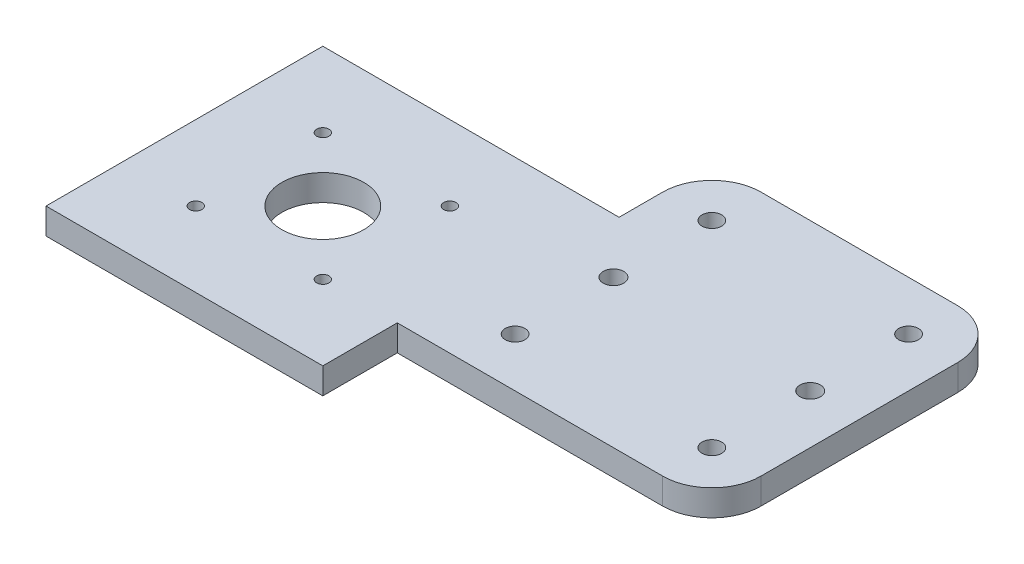
SolidWorks part; units mm, degrees
ref_plane "Front Plane" through (0, 0, 0) normal (0, 0, 1) x (1, 0, 0)
ref_plane "Top Plane" through (0, 0, 0) normal (0, 1, 0) x (1, 0, 0)
ref_plane "Right Plane" through (0, 0, 0) normal (1, 0, 0) x (0, 0, -1)
sketch "Sketch1" plane through (0, 0, 0) normal (0, 1, 0) x (1, 0, 0)
  line L1 (-24, -36) -> (24, -36)
  line L2 (-36, -24) -> (-36, 24)
  line L3 (-24, 36) -> (24, 36)
  line L4 (36, -24) -> (36, 24)
  line L5 (-36, -36) -> (36, 36) construction
  line L6 (-36, 36) -> (36, -36) construction
  arc A0 (24, 36) -> (36, 24) centre (24, 24) cw
  arc A1 (24, -36) -> (36, -24) centre (24, -24) ccw
  arc A2 (-24, -36) -> (-36, -24) centre (-24, -24) cw
  arc A3 (-36, 24) -> (-24, 36) centre (-24, 24) cw
  point P0 (0, 0)
  dimension "D1" = 12
  dimension "D2" = 72
  dimension "D3" = 72
extrude "Boss-Extrude1" add sketch "Sketch1" along normal blind 6.35
sketch "Sketch2" plane through (0, 6.35, 0) normal (0, 1, 0) x (1, 0, 0)
  line L0 (-36, 0) -> (36, 0) construction
  line L1 (-36, 24) -> (-36, -24) construction
  line L2 (36, -24) -> (36, 24) construction
  line L3 (-36, 12) -> (36, 12) construction
  circle A0 centre (-24, 24) radius 12 construction
  circle A1 centre (-24, 24) radius 2.4
  arc A2 (-24, 36) -> (-36, 24) centre (-24, 24) ccw construction
  circle A3 centre (24, 24) radius 2.4
  circle A4 centre (24, -24) radius 2.4
  circle A5 centre (-24, -24) radius 2.4
  dimension "D3" = 4.8
  dimension "D1" = 24
  dimension "D2" = 2
  dimension "D4" = 2
extrude "Cut-Extrude1" cut sketch "Sketch2" against normal through all
sketch "Sketch3" plane through (0, 6.35, 0) normal (0, 1, 0) x (1, 0, 0)
  line L0 (-24, 0) -> (24, 0) construction
  line L1 (-24, 24) -> (-24, -24) construction
  line L2 (24, 24) -> (24, -24) construction
  circle A1 centre (-24, 0) radius 2.5
  circle A3 centre (24, 0) radius 2.5
  dimension "D1" = 5
extrude "Cut-Extrude2" cut sketch "Sketch3" against normal through all
sketch "Sketch4" plane through (0, 6.35, 0) normal (0, 1, 0) x (1, 0, 0)
  line L11 (-108.286, -54.1706) -> (-40.7474, -54.1706)
  line L12 (-108.286, -54.1706) -> (-108.286, 13.368)
  line L13 (-108.286, 13.368) -> (-36, 13.368)
  line L14 (-40.7474, -54.1706) -> (-40.7474, -36)
  line L15 (-108.286, -54.1706) -> (-40.7474, 13.368) construction
  line L16 (-108.286, 13.368) -> (-40.7474, -54.1706) construction
  line L17 (-90.0167, -35.9013) -> (-59.0167, -35.9013) construction
  line L18 (-90.0167, -35.9013) -> (-90.0167, -4.9013) construction
  line L19 (-90.0167, -4.9013) -> (-59.0167, -4.9013) construction
  line L20 (-59.0167, -35.9013) -> (-59.0167, -4.9013) construction
  line L21 (-90.0167, -35.9013) -> (-59.0167, -4.9013) construction
  line L22 (-90.0167, -4.9013) -> (-59.0167, -35.9013) construction
  line L26 (24, 36) -> (-24, 36)
  line L27 (-36, 24) -> (-36, -24)
  line L28 (-24, -36) -> (24, -36)
  line L29 (36, -24) -> (36, 24)
  line L31 (-36, 13.368) -> (-36, -24)
  line L32 (-24, -36) -> (-40.7474, -36)
  circle A0 centre (-90.0167, -4.9013) radius 1.5
  circle A1 centre (-59.0167, -4.9013) radius 1.5
  circle A2 centre (-59.0167, -35.9013) radius 1.5
  circle A3 centre (-90.0167, -35.9013) radius 1.5
  arc A4 (36, 24) -> (24, 36) centre (24, 24) ccw
  arc A5 (-24, 36) -> (-36, 24) centre (-24, 24) ccw
  arc A6 (-36, -24) -> (-24, -36) centre (-24, -24) ccw
  arc A7 (24, -36) -> (36, -24) centre (24, -24) ccw
  arc A10 (-36, -24) -> (-24, -36) centre (-24, -24) ccw
  circle A12 centre (-74.5167, -20.4013) radius 10
  point P0 (-74.5167, -20.4013)
  point P5 (-74.5167, -20.4013)
  point P30 (-57.5452, -31.2955)
  point P31 (-53.8276, -21.1701)
  point P32 (-57.5976, -21.1701)
  point P33 (-74.5167, -20.4013)
  point P35 (-87.6658, -21.997)
  point P36 (-85.7786, -24.4876)
  point P37 (0, 0)
  point P41 (0, 0)
  point P42 (0, 0)
  point P43 (0, 0)
  dimension "D3" = 3
  dimension "D4" = 20
  dimension "D1" = 31
  dimension "D2" = 0
extrude "Boss-Extrude2" add sketch "Sketch4" against normal up to surface (6.35 mm away) up to face at (-24, 0, 2.5)
